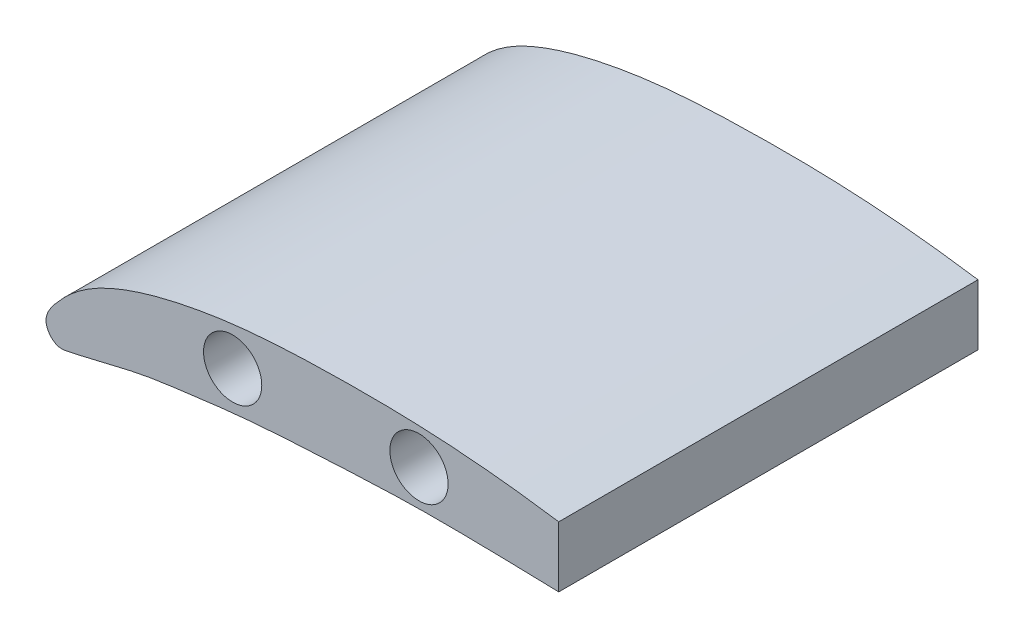
SolidWorks part; units mm, degrees
ref_plane "Front Plane" through (0, 0, 0) normal (0, 0, 1) x (1, 0, 0)
ref_plane "Top Plane" through (0, 0, 0) normal (0, 1, 0) x (1, 0, 0)
ref_plane "Right Plane" through (0, 0, 0) normal (1, 0, 0) x (0, 0, -1)
curve "Curve1"
  spline degree 3 poles (25.4, 0.0889, 0) (24.9755, 0.1879, 0) (24.1284, 0.3854, 0) (22.4316, 0.7474, 0) (20.3056, 1.1527, 0) (17.7661, 1.6728, 0) (15.2225, 2.1285, 0) (12.6828, 2.5208, 0) (10.1333, 2.7153, 0) (7.5886, 2.7177, 0) (5.4641, 2.6194, 0) (3.7724, 2.3478, 0) (2.7142, 2.0863, 0) (1.8702, 1.7836, 0) (1.2225, 1.4719, 0) (0.6864, 1.0854, 0) (0.2512, 0.6226, 0) (-0.1733, 0.0898, 0) (0.2557, -0.4257, 0) (0.7562, -0.3188, 0) (1.2698, -0.1979, 0) (1.905, -0.0426, 0) (2.7433, 0.1487, 0) (3.8055, 0.2872, 0) (5.4925, 0.5064, 0) (7.6119, 0.6227, 0) (10.1512, 0.7472, 0) (12.6929, 0.6952, 0) (15.2354, 0.6324, 0) (17.7755, 0.4534, 0) (20.3173, 0.2785, 0) (22.4335, 0.1017, 0) (24.1313, 0.0327, 0) (24.9769, -0.0484, 0) (25.4, -0.0889, 0) knots 0 0 0 0 0.025045 0.049982 0.099693 0.149405 0.198931 0.248178 0.297011 0.345669 0.394384 0.418982 0.444018 0.456913 0.470405 0.485361 0.494029 0.508284 0.517562 0.523649 0.536105 0.548579 0.561002 0.585562 0.610033 0.658766 0.707435 0.756094 0.804785 0.853571 0.902386 0.951201 0.975578 1 1 1 1
sketch "Sketch1" plane through (0, 0, 0) normal (0, 0, 1) x (1, 0, 0)
  line L0 (25.4, 0.0889) -> (25.4, -0.0889) construction
  line L1 (254, 0.889) -> (254, -0.889)
  line L2 (0, 0) -> (254, 0) construction
  line L3 (127, 0) -> (127, 24.8566) construction
  line L4 (139.7, 0) -> (139.7, 6.6099) construction
  line L5 (139.7, 6.6099) -> (139.7, 23.1662)
  line L6 (50.8, 0) -> (50.8, 4.4198) construction
  line L7 (50.8, 4.4198) -> (50.8, 25.402) construction
  line L8 (101.6, 0) -> (101.6, 7.1792) construction
  line L9 (101.6, 7.1792) -> (101.6, 26.8232) construction
  line L10 (147.4927, 0) -> (147.4927, 6.3416) construction
  line L11 (147.4927, 6.3416) -> (147.4927, 21.9573) construction
  circle A0 centre (50.8, 14.9109) radius 7.9375
  circle A1 centre (101.6, 17.0012) radius 7.9375
  circle A2 centre (147.4927, 14.1494) radius 2.2522
  spline S0 degree 3 poles (566.0092, 1924.6845) (86.0699, -40.1547) (57.6216, -6.7602) (22.4316, 0.7474) (20.3056, 1.1527) (17.7661, 1.6728) (15.2225, 2.1285) (12.6828, 2.5208) (10.1333, 2.7153) (7.5886, 2.7177) (5.4641, 2.6194) (3.7724, 2.3478) (2.7142, 2.0863) (1.8702, 1.7836) (1.2225, 1.4719) (0.6864, 1.0854) (0.2512, 0.6226) (-0.1733, 0.0898) (0.2557, -0.4257) (0.7562, -0.3188) (1.2698, -0.1979) (1.905, -0.0426) (2.7433, 0.1487) (3.8055, 0.2872) (5.4925, 0.5064) (7.6119, 0.6227) (10.1512, 0.7472) (12.6929, 0.6952) (15.2354, 0.6324) (17.7755, 0.4534) (20.3173, 0.2785) (22.4335, 0.1017) (47.7216, -0.9264) (69.4681, -40.4772) (235.2289, 1988.3291) knots -1.967795 -1.967795 -1.967795 -1.967795 0.025045 0.049982 0.099693 0.149405 0.198931 0.248178 0.297011 0.345669 0.394384 0.418982 0.444018 0.456913 0.470405 0.485361 0.494029 0.508284 0.517562 0.523649 0.536105 0.548579 0.561002 0.585562 0.610033 0.658766 0.707435 0.756094 0.804785 0.853571 0.902386 0.951201 0.975578 2.356301 2.356301 2.356301 2.356301 only from (25.4, 0.0889) to (25.4, -0.0889) construction
  spline S1 degree 3 poles (25.4, 0.0889) (24.9755, 0.1879) (24.1284, 0.3854) (22.4316, 0.7474) (20.3056, 1.1527) (17.7661, 1.6728) (15.2225, 2.1285) (12.6828, 2.5208) (10.1333, 2.7153) (7.5886, 2.7177) (5.4641, 2.6194) (3.7724, 2.3478) (2.7142, 2.0863) (1.8702, 1.7836) (1.2225, 1.4719) (0.6864, 1.0854) (0.2512, 0.6226) (-0.1733, 0.0898) (0.2557, -0.4257) (0.7562, -0.3188) (1.2698, -0.1979) (1.905, -0.0426) (2.7433, 0.1487) (3.8055, 0.2872) (5.4925, 0.5064) (7.6119, 0.6227) (10.1512, 0.7472) (12.6929, 0.6952) (15.2354, 0.6324) (17.7755, 0.4534) (20.3173, 0.2785) (22.4335, 0.1017) (24.1313, 0.0327) (24.9769, -0.0484) (25.4, -0.0889) knots 0 0 0 0 0.025045 0.049982 0.099693 0.149405 0.198931 0.248178 0.297011 0.345669 0.394384 0.418982 0.444018 0.456913 0.470405 0.485361 0.494029 0.508284 0.517562 0.523649 0.536105 0.548579 0.561002 0.585562 0.610033 0.658766 0.707435 0.756094 0.804785 0.853571 0.902386 0.951201 0.975578 1 1 1 1 construction
  spline S2 degree 3 poles (254, 0.889) (249.7553, 1.8786) (241.2842, 3.8535) (224.3158, 7.4736) (203.0565, 11.5272) (177.6613, 16.7283) (152.2253, 21.2846) (126.8284, 25.208) (101.3332, 27.1529) (75.8856, 27.1773) (54.6411, 26.1945) (37.7241, 23.4783) (27.1418, 20.8628) (18.7017, 17.8364) (12.2246, 14.7192) (6.8643, 10.8535) (2.5124, 6.2258) (-1.7329, 0.8975) (2.5571, -4.257) (7.5624, -3.188) (12.6982, -1.9788) (19.0498, -0.4259) (27.4332, 1.4865) (38.0551, 2.8725) (54.9249, 5.0635) (76.1187, 6.227) (101.5119, 7.4722) (126.9288, 6.9519) (152.354, 6.3244) (177.755, 4.534) (203.1733, 2.7851) (224.3353, 1.0168) (241.3134, 0.3266) (249.7685, -0.4836) (254, -0.889) knots 0 0 0 0 0.025045 0.049982 0.099693 0.149405 0.198931 0.248178 0.297011 0.345669 0.394384 0.418982 0.444018 0.456913 0.470405 0.485361 0.494029 0.508284 0.517562 0.523649 0.536105 0.548579 0.561002 0.585562 0.610033 0.658766 0.707435 0.756094 0.804785 0.853571 0.902386 0.951201 0.975578 1 1 1 1
  point P9 (139.7, 0)
  point P12 (50.8, 0)
  point P19 (50.8, 22.8484)
  point P20 (50.8, 6.9734)
  point P21 (101.6, 0)
  point P27 (147.4927, 0)
  dimension "D5" = 15.875
  dimension "D7" = 15.875
  dimension "D1" = 254
  dimension "D2" = 24.8566
  dimension "D3" = 139.7
  dimension "D4" = 50.8
  dimension "D6" = 50.8
  dimension "D8" = 147.4927
extrude "Boss-Extrude1" add sketch "Sketch1" along normal blind 114.3 contours L5 S2 region at (70.4556, 14.021, 0)
